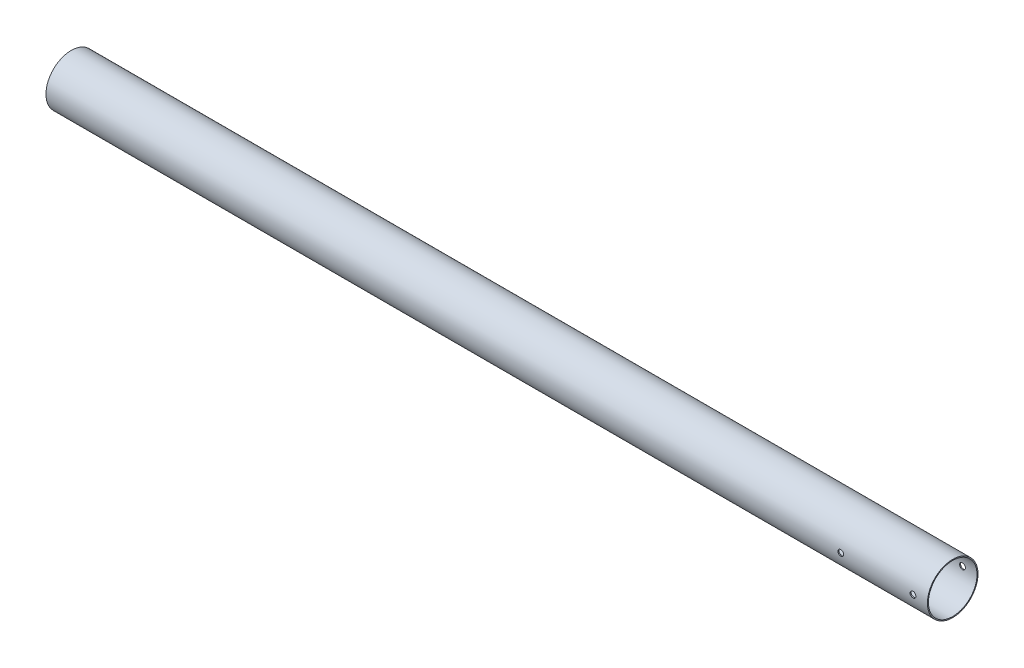
SolidWorks part; units mm, degrees
ref_plane "Front" through (0, 0, 0) normal (0, 0, 1) x (1, 0, 0)
ref_plane "Top" through (0, 0, 0) normal (0, 1, 0) x (1, 0, 0)
ref_plane "Right" through (0, 0, 0) normal (1, 0, 0) x (0, 0, -1)
sketch "Sketch1" plane through (0, 0, 0) normal (1, 0, 0) x (0, 0, -1)
  line L0 (21.336, 0) -> (22.225, 0) construction
  line L1 (21.336, 0) -> (22.225, 0) construction
  line L2 (21.7805, 0) -> (21.7805, 1.0672) construction
  circle A0 centre (0, 0) radius 22.225
  circle A1 centre (0, 0) radius 21.336
  point P4 (22.225, 0)
  point P5 (21.336, 0)
  dimension "OD" = 44.45
  dimension "ID" = 42.672
  dimension "Wall Thickness" = 0.889
sketch "Sketch2" plane through (0, 0, 0) normal (0, 0, 1) x (1, 0, 0)
  line L0 (-387.35, 0) -> (387.35, 0) construction
  point P2 (-331.7875, 0)
  point P3 (331.7875, 0)
  dimension "D1" = 55.5625
  dimension "D2" = 55.5625
sketch "Sketch3" plane through (0, 0, 0) normal (1, 0, 0) x (0, 0, -1)
  circle A0 centre (0, 0) radius 21.336 construction
  circle A1 centre (0, 0) radius 22.225 construction
  circle A2 centre (0, 0) radius 21.336
  circle A3 centre (0, 0) radius 22.225
extrude "Boss-Extrude1" add sketch "Sketch3" along normal mid plane 774.7
sketch "Sketch4" plane through (0, 0, 0) normal (0, 0, 1) x (1, 0, 0)
  line L0 (387.35, 0) -> (311.15, 0) construction
  line L7 (387.35, -22.225) -> (387.35, 22.225) construction
  circle A0 centre (311.15, 0) radius 2.5527
  circle A1 centre (374.65, 0) radius 2.5527
  dimension "D3" = 76.2
  dimension "D1" = 5.1054
  dimension "D2" = 12.7
extrude "Cut-Extrude1" cut sketch "Sketch4" along normal through all both and the other way through all
equation "\"D1@Boss-Extrude1\"=\"Length@Sketch2\""
equation "\"D1@Sketch2\"=\"OD@Sketch1\"*1.25"
equation "\"D2@Sketch2\"=\"D1@Sketch2\""
